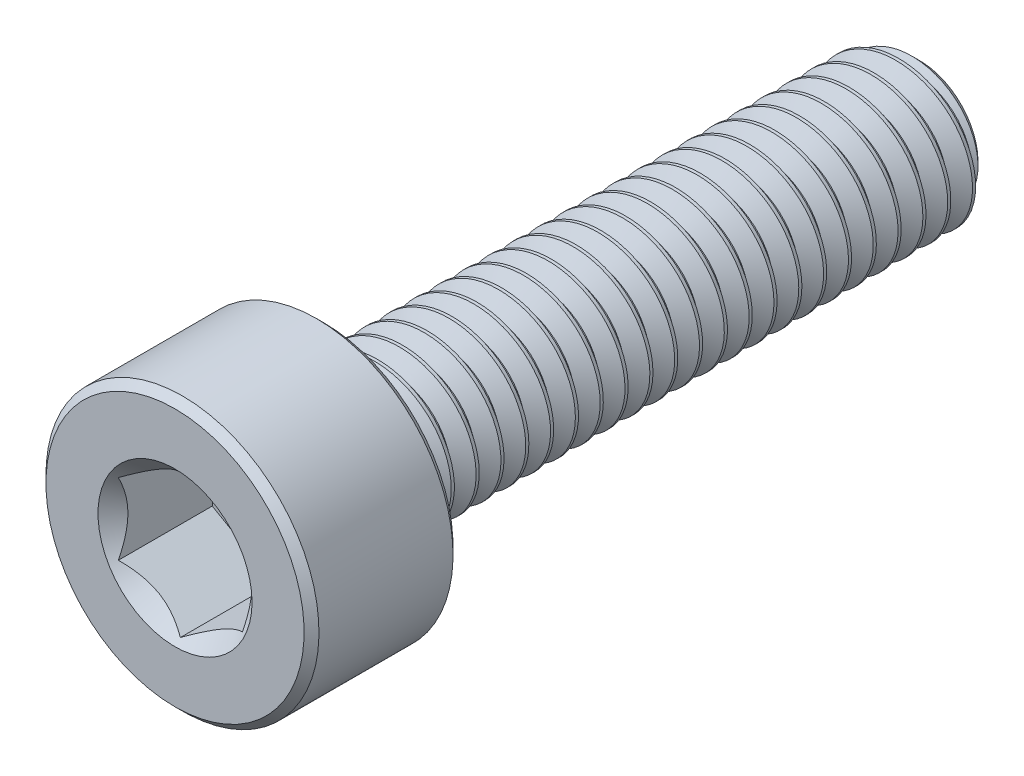
SolidWorks part; units mm, degrees
ref_plane "Front Plane" through (0, 0, 0) normal (0, 0, 1) x (1, 0, 0)
ref_plane "Top Plane" through (0, 0, 0) normal (0, 1, 0) x (1, 0, 0)
ref_plane "Right Plane" through (0, 0, 0) normal (1, 0, 0) x (0, 0, -1)
sketch "Sketch1" plane through (0, 0, 0) normal (1, 0, 0) x (0, 0, -1)
  line L0 (-7.5, 0) -> (7.5, 0) construction
  line L1 (7.5, 0) -> (7.5, 1.1752) construction
  line L2 (7.5, 1.1752) -> (7.1752, 1.5) construction
  line L3 (7.1752, 1.5) -> (7.125, 1.5) construction
  line L4 (7.125, 1.5) -> (-4.5, 1.5) construction
  line L5 (-4.5, 1.5) -> (-4.5, 2.75) construction
  line L6 (-4.5, 2.75) -> (-7.5, 2.75) construction
  line L7 (-7.5, 2.75) -> (-7.5, 0) construction
  line L8 (7.5, 1.1752) -> (7.5, 1.5) construction
  line L9 (7.4687, 1.5541) -> (7.7187, 1.1211) construction
  line L10 (7.7187, 1.1211) -> (7.9687, 1.5541) construction
  line L11 (7.9687, 1.5541) -> (7.4687, 1.5541) construction
  line L12 (7.7187, 1.5541) -> (7.7188, 1.5) construction
  line L13 (7.7187, 1.1211) -> (7.7187, 1.1752) construction
  line L14 (7.6875, 1.1752) -> (7.75, 1.1752) construction
  line L15 (7.5, 1.5) -> (7.9375, 1.5) construction
  line L16 (7.4844, 1.5271) -> (7.9531, 1.5271) construction
  line L17 (7.5, 0) -> (7.5, -1.5) construction
  line L18 (-4.65, 2.75) -> (-4.5, 2.6) construction
  line L19 (-7.35, 2.75) -> (-7.5, 2.6) construction
  line L20 (-4.5, 1.5) -> (-4.5, 0) construction
  line L21 (-4.5, 0.75) -> (-0.5, 0.75) construction
  line L22 (-0.5, 0.75) -> (3.5, 0.75) construction
  line L23 (3.5, 0.75) -> (7.5, 0.75) construction
  line L24 (-0.5, 0.75) -> (-0.5, 1.5) construction
  line L25 (-0.5, 1.5) -> (-0.5, 2.75) construction
  line L26 (3.5, 0.75) -> (3.5, 2.75) construction
  point P0 (-7.5, 1.25)
  point P3 (6.25, 1.5)
  point P4 (0, 0)
  point P18 (3.5, 1.5)
  point P22 (7.7187, 1.1752)
  point P24 (7.125, 1.5)
  point P25 (7.7188, 1.5)
  point P28 (7.7188, 1.5271)
  point P29 (6.25, -1.5)
  point P30 (-0.5, 1.5)
  point P31 (-6, 2.75)
  point P37 (-5.025, 2.75)
  point P38 (-7.275, 2.75)
  point P45 (-0.5, 0.75)
  point P46 (3.5, 0.75)
  dimension "D2" = 0.0625
  dimension "D7" = 0.15
  dimension "D8" = 0.15
  dimension "D9" = 0.15
  dimension "D10" = 0.075
  dimension "D11" = 0.375
  dimension "Drive Size" = 2.5
  dimension "Head Diameter" = 5.5
  dimension "Head Height" = 3
  dimension "Thread Pitch" = 0.5
  dimension "Thread Size" = 3
  dimension "Length" = 12
  dimension "D12" = 0.375
  dimension "D4" = 1.25
  dimension "D3" = 45
sketch "Sketch2" plane through (0, 0, 0) normal (1, 0, 0) x (0, 0, -1)
  line L0 (-7.5, 0) -> (-7.5, 2.6)
  line L1 (-7.35, 2.75) -> (-4.65, 2.75)
  line L2 (-4.5, 2.6) -> (-4.5, 1.65)
  line L4 (7.1752, 1.5) -> (7.5, 1.1752)
  line L5 (7.5, 1.1752) -> (7.5, 0)
  line L6 (-4.5, 2.75) -> (-7.5, 2.75) construction
  line L7 (7.5, 0) -> (-7.5, 0)
  line L8 (-7.35, 2.75) -> (-7.5, 2.6) construction
  line L10 (-7.35, 2.75) -> (-7.5, 2.6)
  line L14 (-4.65, 2.75) -> (-4.5, 2.6) construction
  line L16 (-4.65, 2.75) -> (-4.5, 2.6)
  line L17 (-4.5, 1.5) -> (-4.5, 2.75) construction
  line L19 (-4.35, 1.5) -> (7.1752, 1.5)
  line L20 (7.125, 1.5) -> (-4.5, 1.5) construction
  arc A1 (-4.5, 1.65) -> (-4.35, 1.5) centre (-4.35, 1.65) ccw
revolve "Revolve1" add sketch "Sketch2" angle 360 about L7
sketch "Sketch3" plane through (0, 0, 7.5) normal (0, 0, 1) x (1, 0, 0)
  line L1 (1.25, -0.7217) -> (1.25, 0.7217)
  line L2 (1.25, 0.7217) -> (0, 1.4434)
  line L3 (0, 1.4434) -> (-1.25, 0.7217)
  line L4 (-1.25, 0.7217) -> (-1.25, -0.7217)
  line L5 (-1.25, -0.7217) -> (0, -1.4434)
  line L6 (0, -1.4434) -> (1.25, -0.7217)
  circle A0 centre (0, 0) radius 1.25 construction
  circle A1 centre (0, 0) radius 2.75 construction
  circle A2 centre (0, 0) radius 2.75 construction
  circle A3 centre (0, 0) radius 1.4434 construction
  point P13 (0, 0)
  dimension "D1" = 2.8868
extrude "Cut-Extrude1" cut sketch "Sketch3" against normal offset from surface (2 mm away) 1 up to face at (0, 2.6, 4.5)
sketch "Sketch4" plane through (0, 0, 7.5) normal (0, 0, 1) x (1, 0, 0)
  circle A0 centre (0, 0) radius 1.5516
  dimension "D1" = 3.1033
extrude "Cut-Extrude2" cut sketch "Sketch4" against normal up to vertex (1.5 mm away) draft 45 up to point (0, 2.75, 6)
sketch "Sketch11" plane through (0, 0, 0) normal (1, 0, 0) x (0, 0, -1)
  line L0 (-7.5, 0) -> (7.5, 0) construction
  line L1 (-7.5, 0) -> (7.5, 0) construction
  line L2 (-2.25, 0) -> (-2.25, 1.5) construction
  line L3 (7.125, 1.5) -> (-4.5, 1.5) construction
  line L4 (5.25, 0) -> (5.25, 1.5) construction
  line L6 (7.5, 1.1752) -> (7.5, 1.5) construction
  point P2 (-2.25, 0)
  point P3 (5.25, 0)
  dimension "D1" = 2.25
  dimension "D2" = 2.25
sketch "Sketch6" plane through (0, 0, -7.5) normal (0, 0, -1) x (-1, 0, 0)
  circle A0 centre (0, 0) radius 1.5
curve "Helix/Spiral1" pitch 0.5 height 12.5 radius 1.5 centre (0, 0, -7.5) axis (0, 0, 1) start towards (0, 1, 0)
sketch "Sketch10" plane through (0, 0, 0) normal (1, 0, 0) x (0, 0, -1)
  line L0 (-4.35, -2.75) -> (-4.35, 2.75)
  line L5 (-7.5, 0) -> (7.5, 0) construction
  line L6 (-4.35, 1.5) -> (-4.35, -1.5) construction
  point P3 (-4.35, 0)
split "Split1" trim tools "Sketch10" bodies to split 106 resulting bodies 114 115
sketch "Sketch7" plane through (0, 0, 0) normal (1, 0, 0) x (0, 0, -1)
  line L0 (7.4844, 1.5271) -> (7.9531, 1.5271)
  line L1 (7.9531, 1.5271) -> (7.75, 1.1752)
  line L2 (7.75, 1.1752) -> (7.6875, 1.1752)
  line L3 (7.6875, 1.1752) -> (7.4844, 1.5271)
sweep "Cut-Sweep1" cut profiles "Sketch7" path "Helix/Spiral1" align with end faces yes
sketch "Sketch8" plane through (0, 0, 0) normal (1, 0, 0) x (0, 0, -1)
  line L0 (-4.5, 0) -> (-4.5, 1.5)
  line L1 (-4.35, -1.5) -> (-4.35, 1.5) construction
  line L2 (-4.5, 1.5) -> (-4.35, 1.5)
  line L4 (-4.35, 1.5) -> (-3.484, 0)
  line L5 (-3.484, 0) -> (-4.5, 0)
  line L6 (7.125, 1.5) -> (-4.5, 1.5) construction
  line L7 (-7.5, 0) -> (7.5, 0) construction
  dimension "D1" = 60
revolve "Revolve2" add sketch "Sketch8" angle 360 about L5
equation "\"D2@Sketch1\" = \"Thread Pitch@Sketch1\" / 8"
equation "\"D4@Helix/Spiral1\" = \"Thread Pitch@Sketch1\""
equation "\"D7@Sketch1\" = \"Head Height@Sketch1\" * .05"
equation "\"D8@Sketch1\"=\"D7@Sketch1\""
equation "\"D9@Sketch1\"=\"D7@Sketch1\""
equation "\"D10@Sketch1\"=\"D7@Sketch1\"/2"
equation "\"D11@Sketch1\"=\"D10@Sketch1\"*5"
equation "\"D4@Sketch1\"=\"Thread Pitch@Sketch1\"*2.5"
equation "\"D12@Sketch1\"=\"Thread Pitch@Sketch1\"*.75"
equation "\"D3@Helix/Spiral1\"=\"Length@Sketch1\"+\"Thread Pitch@Sketch1\""
equation "\"D3@Sketch2\"=\"Thread Size@Sketch1\"*0.05"
equation "\"D1@Sketch11\"=\"Length@Sketch1\"*0.1875"
equation "\"D2@Sketch11\"=\"D1@Sketch11\""
equation "\"D1@Sketch4\"=\"D1@Sketch3\"*1.075"
